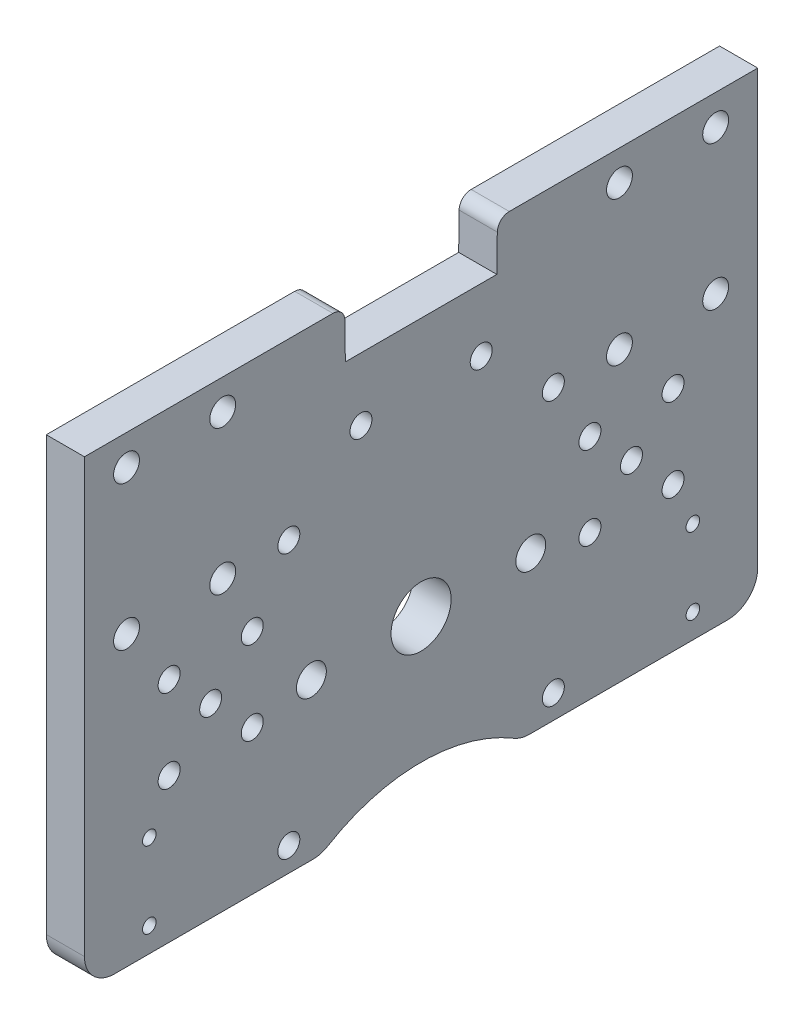
SolidWorks part; units mm, degrees
ref_plane "Front Plane" through (0, 0, 0) normal (0, 0, 1) x (1, 0, 0)
ref_plane "Top Plane" through (0, 0, 0) normal (0, 1, 0) x (1, 0, 0)
ref_plane "Right Plane" through (0, 0, 0) normal (1, 0, 0) x (0, 0, -1)
sketch "Sketch1" plane through (0, 0, 0) normal (1, 0, 0) x (0, 0, -1)
  line L1 (-56, -26) -> (56, -26)
  line L2 (-56, -26) -> (-56, 51)
  line L3 (-56, 51) -> (56, 51)
  line L4 (56, -26) -> (56, 51)
  point P0 (0, 0)
  point P6 (0, -26)
  dimension "D1" = 77
  dimension "D2" = 112
  dimension "D3" = 26
extrude "Boss-Extrude1" add sketch "Sketch1" along normal blind 6.35
sketch "Sketch2" plane through (6.35, 0, 0) normal (1, 0, 0) x (0, 0, -1)
  line L1 (-22, -22) -> (22, -22) construction
  line L2 (-22, -22) -> (-22, 22) construction
  line L3 (-22, 22) -> (22, 22) construction
  line L4 (22, -22) -> (22, 22) construction
  line L5 (-22, -22) -> (22, 22) construction
  line L6 (-22, 22) -> (22, -22) construction
  point P0 (0, 0)
  dimension "D1" = 44
  dimension "D2" = 44
hole_wizard "#6 Clearance Hole1" positions "Sketch4" profile "Sketch3" hole size "#6" standard "ANSI Inch" end condition through all
sketch "Sketch4" plane through (6.35, 0, 0) normal (1, 0, 0) x (0, 0, -1)
  point P0 (-22, 22)
  point P3 (22, 22)
  point P6 (22, -22)
  point P9 (-22, -22)
sketch "Sketch3" plane through (6.35, 22, 22) normal (0, 1, 0) x (0, 0, -1)
  line L0 (0, 0) -> (0, 6.35)
  line L1 (0, 6.35) -> (1.8288, 6.35)
  line L2 (1.8288, 6.35) -> (1.8288, 0)
  line L5 (1.8288, 0) -> (0, 0)
  line L11 (0, -6.35) -> (0, 107.95) construction
  dimension "Thru Hole Dia." = 3.6576
  dimension "Thru Hole Depth" = 6.35
sketch "Sketch5" plane through (6.35, 0, 0) normal (1, 0, 0) x (0, 0, -1)
  circle A0 centre (0, 0) radius 5
  dimension "D1" = 10
extrude "Cut-Extrude1" cut sketch "Sketch5" against normal through all
sketch "Sketch7" plane through (6.35, 0, 0) normal (1, 0, 0) x (0, 0, -1)
  line L0 (-41.9148, -1.9448) -> (-41.9148, 11.8848) construction
  line L1 (-41.9148, -1.9448) -> (-28.0852, -1.9448) construction
  line L2 (-41.9148, 11.8848) -> (-28.0852, 11.8848) construction
  line L3 (-28.0852, -1.9448) -> (-28.0852, 11.8848) construction
  line L4 (-41.9148, -1.9448) -> (-28.0852, 11.8848) construction
  line L5 (-41.9148, 11.8848) -> (-28.0852, -1.9448) construction
  line L6 (41.9148, -1.9448) -> (41.9148, 11.8848) construction
  line L7 (41.9148, -1.9448) -> (28.0852, -1.9448) construction
  line L8 (41.9148, 11.8848) -> (28.0852, 11.8848) construction
  line L9 (28.0852, -1.9448) -> (28.0852, 11.8848) construction
  line L10 (41.9148, -1.9448) -> (28.0852, 11.8848) construction
  line L11 (41.9148, 11.8848) -> (28.0852, -1.9448) construction
  line L12 (-35, 4.97) -> (35, 4.97) construction
  point P1 (-35, 4.97)
  point P2 (35, 4.97)
  point P8 (0, 4.97)
  dimension "D1" = 19.558
  dimension "D2" = 19.558
  dimension "D3" = 70
  dimension "D4" = 4.97
hole_wizard "#6 Clearance Hole2" positions "Sketch9" profile "Sketch8" hole size "#6" standard "ANSI Inch" end condition through all
sketch "Sketch9" plane through (6.35, 0, 0) normal (1, 0, 0) x (0, 0, -1)
  point P0 (-41.9148, 11.8848)
  point P3 (-28.0852, 11.8848)
  point P6 (-28.0852, -1.9448)
  point P9 (-41.9148, -1.9448)
  point P12 (28.0852, 11.8848)
  point P15 (28.0852, -1.9448)
  point P18 (41.9148, -1.9448)
  point P21 (41.9148, 11.8848)
  point P24 (-35, 4.97)
  point P27 (35, 4.97)
sketch "Sketch8" plane through (6.35, 11.8848, 41.9148) normal (0, 1, 0) x (0, 0, -1)
  line L0 (0, 0) -> (0, 6.35)
  line L1 (0, 6.35) -> (1.8288, 6.35)
  line L2 (1.8288, 6.35) -> (1.8288, 0)
  line L5 (1.8288, 0) -> (0, 0)
  line L11 (0, -6.35) -> (0, 107.95) construction
  dimension "Thru Hole Dia." = 3.6576
  dimension "Thru Hole Depth" = 6.35
sketch "Sketch11" plane through (0, 0, 0) normal (-1, 0, 0) x (0, 0, 1)
  line L0 (-18.25, 0) -> (18.25, 0) construction
  point P4 (0, 0)
  dimension "D1" = 36.5
hole_wizard "#10 Clearance Hole1" positions "Sketch13" profile "Sketch12" hole size "#10" standard "ANSI Inch" end condition through all
sketch "Sketch13" plane through (0, 0, 0) normal (-1, 0, 0) x (0, 0, 1)
  point P0 (18.25, 0)
  point P3 (-18.25, 0)
sketch "Sketch12" plane through (0, 0, 18.25) normal (0, 1, 0) x (0, 0, 1)
  line L0 (0, 0) -> (0, 6.35)
  line L1 (0, 6.35) -> (2.4892, 6.35)
  line L2 (2.4892, 6.35) -> (2.4892, 0)
  line L5 (2.4892, 0) -> (0, 0)
  line L11 (0, -6.35) -> (0, 107.95) construction
  dimension "Thru Hole Dia." = 4.9784
  dimension "Thru Hole Depth" = 6.35
sketch "Sketch20" plane through (0, 0, 0) normal (-1, 0, 0) x (0, 0, 1)
  line L0 (56, 51) -> (56, -26) construction
  line L1 (49, 45.97) -> (33, 45.97) construction
  line L2 (49, 45.97) -> (49, 21.97) construction
  line L3 (49, 21.97) -> (33, 21.97) construction
  line L4 (33, 45.97) -> (33, 21.97) construction
  line L5 (-33, 45.97) -> (-49, 45.97) construction
  line L6 (-33, 45.97) -> (-33, 21.97) construction
  line L7 (-33, 21.97) -> (-49, 21.97) construction
  line L8 (-49, 45.97) -> (-49, 21.97) construction
  line L9 (-56, -26) -> (-56, 51) construction
  line L10 (-56, 51) -> (56, 51) construction
  dimension "D1" = 16
  dimension "D2" = 24
  dimension "D3" = 7
  dimension "D4" = 7
  dimension "D5" = 5.03
hole_wizard "#8 Clearance Hole2" positions "3DSketch3" profile "Sketch21" hole size "#8" standard "ANSI Inch" end condition through all
sketch3d "3DSketch3"
  point P0 (0, 45.97, 49)
  point P3 (0, 45.97, 33)
  point P6 (0, 21.97, 33)
  point P9 (0, 21.97, 49)
  point P12 (0, 45.97, -33)
  point P15 (0, 21.97, -33)
  point P18 (0, 21.97, -49)
  point P21 (0, 45.97, -49)
sketch "Sketch21" plane through (0, 45.97, 49) normal (0, 1, 0) x (0, 0, 1)
  line L0 (0, 0) -> (0, 6.35)
  line L1 (0, 6.35) -> (2.1526, 6.35)
  line L2 (2.1526, 6.35) -> (2.1526, 0)
  line L5 (2.1526, 0) -> (0, 0)
  line L11 (0, -6.35) -> (0, 107.95) construction
  dimension "Thru Hole Dia." = 4.3053
  dimension "Thru Hole Depth" = 6.35
sketch "Sketch22" plane through (0, 0, 0) normal (-1, 0, 0) x (0, 0, 1)
  line L0 (12.7, 51) -> (-12.7, 51)
  line L1 (-56, 51) -> (56, 51) construction
  line L2 (-12.7, 51) -> (-12.6, 42.97)
  line L3 (-12.6, 42.97) -> (12.6, 42.97)
  line L4 (12.6, 42.97) -> (12.7, 51)
  point P4 (0, 42.97)
  point P7 (0, 51)
  dimension "D1" = 25.4
  dimension "D2" = 25.2
  dimension "D3" = 8.03
extrude "Cut-Extrude2" cut sketch "Sketch22" against normal through all
sketch "Sketch23" plane through (0, 0, 0) normal (-1, 0, 0) x (0, 0, 1)
  line L0 (10, 32.5052) -> (-10, 32.5052) construction
  line L1 (-12.6, 42.97) -> (12.6, 42.97) construction
  point P2 (0, 32.5052)
  dimension "D1" = 10.4648
  dimension "D2" = 20
hole_wizard "#6 Clearance Hole3" positions "3DSketch4" profile "Sketch24" hole size "#6" standard "ANSI Inch" end condition through all
sketch3d "3DSketch4"
  point P0 (0, 32.5052, 10)
  point P3 (0, 32.5052, -10)
sketch "Sketch24" plane through (0, 32.5052, 10) normal (0, 1, 0) x (0, 0, 1)
  line L0 (0, 0) -> (0, 6.35)
  line L1 (0, 6.35) -> (1.8288, 6.35)
  line L2 (1.8288, 6.35) -> (1.8288, 0)
  line L5 (1.8288, 0) -> (0, 0)
  line L11 (0, -6.35) -> (0, 107.95) construction
  dimension "Thru Hole Dia." = 3.6576
  dimension "Thru Hole Depth" = 6.35
fillet "Fillet2" radius 2 2 edges at (3.175, 51, -12.7) (3.175, 51, 12.7)
sketch "Sketch25" plane through (0, 0, 0) normal (-1, 0, 0) x (0, 0, 1)
  line L0 (56, -26) -> (-56, -26) construction
  circle A0 centre (0, -51) radius 30
  point P6 (0, -26)
  dimension "D1" = 60
  dimension "D2" = 25
extrude "Cut-Extrude3" cut sketch "Sketch25" against normal through all
fillet "Fillet1" radius 5 4 edges at (3.175, -26, -56) (3.175, -26, 56) (3.175, -26, -16.5831) (3.175, -26, 16.5831)
sketch "Sketch26" plane through (0, 0, 0) normal (-1, 0, 0) x (0, 0, 1)
  line L0 (45.205, -9.254) -> (45.205, -21.954) construction
  line L1 (56, 51) -> (56, -21) construction
  circle A1 centre (35, 4.97) radius 1.8288 construction
  point P2 (45.205, -15.604)
  dimension "D1" = 12.7
  dimension "D2" = 20.574
  dimension "D3" = 10.795
hole_wizard "Tap Drill for #4-40 Tap1" positions "3DSketch5" profile "Sketch27" hole size "#4-40" standard "ANSI Inch" end condition through all
sketch3d "3DSketch5"
  point P0 (0, -21.954, 45.205)
  point P3 (0, -9.254, 45.205)
sketch "Sketch27" plane through (0, -21.954, 45.205) normal (0, 1, 0) x (0, 0, 1)
  line L0 (0, 0) -> (0, 6.35)
  line L1 (0, 6.35) -> (1.1303, 6.35)
  line L2 (1.1303, 6.35) -> (1.1303, 0)
  line L5 (1.1303, 0) -> (0, 0)
  line L11 (0, -6.35) -> (0, 107.95) construction
  dimension "Thru Hole Dia." = 2.2606
  dimension "Thru Hole Depth" = 6.35
mirror "Mirror1" about plane through (0, 0, 0) normal (0, 0, 1) of "Tap Drill for #4-40 Tap1"
